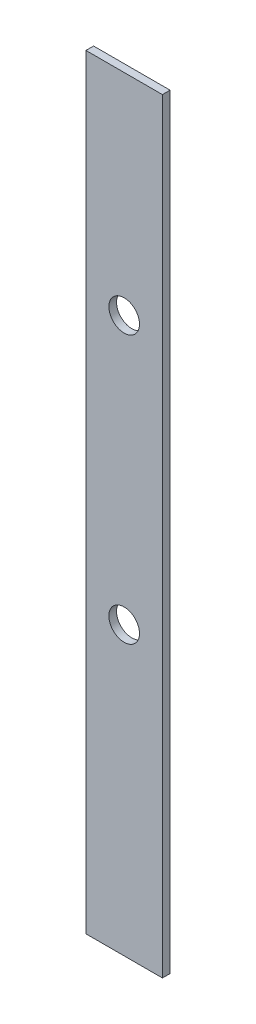
SolidWorks part; units mm, degrees
ref_plane "Front Plane" through (0, 0, 0) normal (0, 0, 1) x (1, 0, 0)
ref_plane "Top Plane" through (0, 0, 0) normal (0, 1, 0) x (1, 0, 0)
ref_plane "Right Plane" through (0, 0, 0) normal (1, 0, 0) x (0, 0, -1)
sketch "Sketch1" plane through (0, 0, 0) normal (0, 0, 1) x (1, 0, 0)
  line L0 (0, 0) -> (20, 0) construction
  line L1 (-20, 140) -> (20, 140) construction
  line L2 (-20, 140) -> (-20, -140)
  line L3 (-20, -140) -> (20, -140) construction
  line L4 (20, 140) -> (20, -140)
  line L5 (-20, 140) -> (20, -140) construction
  line L6 (-20, -140) -> (20, 140) construction
  line L9 (20, -200) -> (20, -140)
  line L10 (-20, -200) -> (-20, -140)
  line L11 (20, 140) -> (20, 200)
  line L12 (-20, 140) -> (-20, 200)
  line L13 (-20, -200) -> (20, -200)
  line L14 (-20, 200) -> (20, 200)
  point P0 (0, 0)
  dimension "D1" = 280
  dimension "D2" = 40
extrude "Boss-Extrude1" add sketch "Sketch1" along normal blind 4 contours L4 L9 L13 L10 L2 L12 L14 L11
ref_plane "Plane1" through (0, 0, 0) normal (0, 0, -1) x (-1, 0, 0)
sketch "Sketch3" plane through (0, 0, 0) normal (0, 0, -1) x (-1, 0, 0)
  line L0 (20, 90) -> (-20, 90) construction
  line L1 (-20, -50) -> (20, -50) construction
  circle A0 centre (0, 90) radius 8
  circle A1 centre (0, -50) radius 8
  dimension "D2" = 140
extrude "Boss-Extrude2" add sketch "Sketch3" against normal blind 4
extrude "Cut-Extrude1" cut sketch "Sketch3<2>" against normal blind 4
sketch "Sketch3<2>" plane through (0, 0, 0) normal (0, 0, -1) x (-1, 0, 0) same geometry as "Sketch3"
